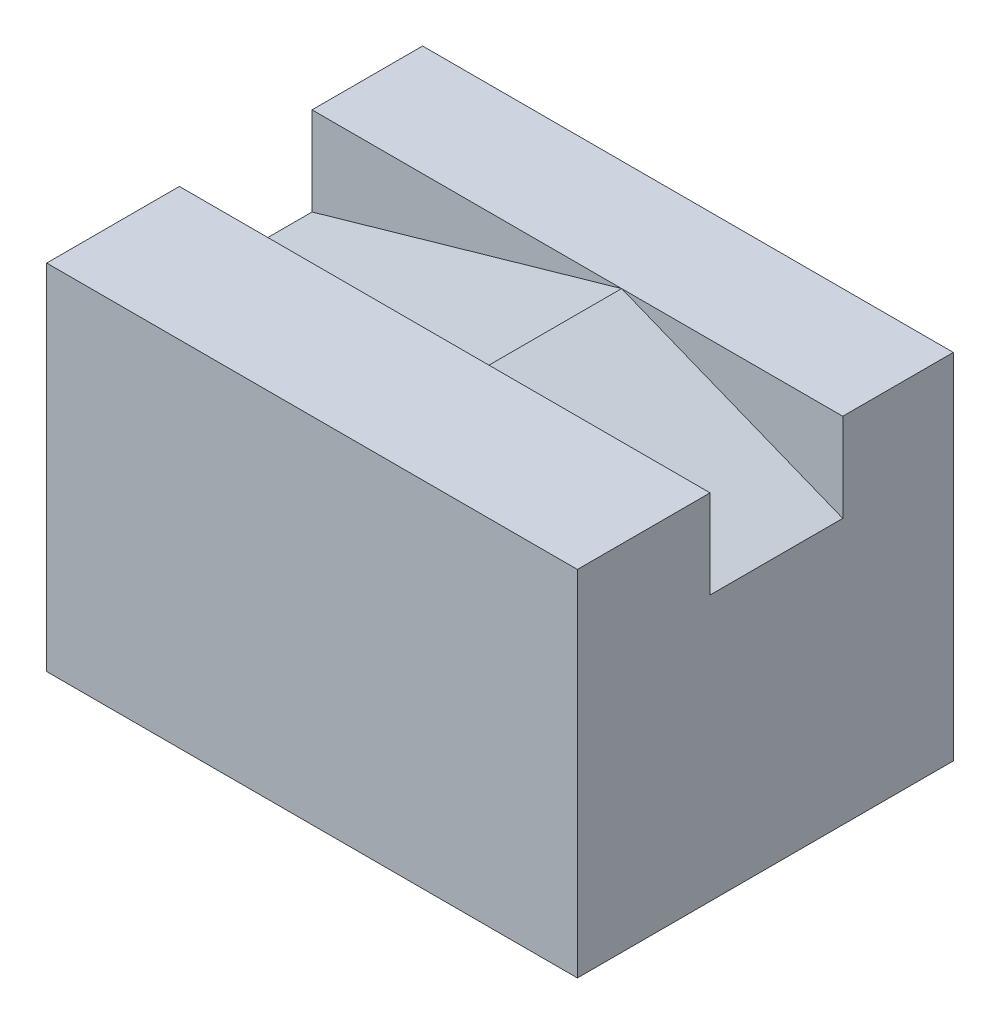
SolidWorks part; units mm, degrees
ref_plane "Front Plane" through (0, 0, 0) normal (0, 0, 1) x (1, 0, 0)
ref_plane "Top Plane" through (0, 0, 0) normal (0, 1, 0) x (1, 0, 0)
ref_plane "Right Plane" through (0, 0, 0) normal (1, 0, 0) x (0, 0, -1)
sketch "Sketch1" plane through (0, 0, 0) normal (0, 0, 1) x (1, 0, 0)
  line L0 (-3, 1) -> (0.5, 2)
  line L1 (-3, -2) -> (3, -2)
  line L2 (-3, -2) -> (-3, 2)
  line L3 (-3, 2) -> (3, 2)
  line L4 (3, -2) -> (3, 2)
  line L5 (-3, -2) -> (3, 2) construction
  line L6 (-3, 2) -> (3, -2) construction
  line L7 (0.5, 2) -> (3, 1)
  point P0 (0, 0)
  point P9 (0, 0)
  dimension "D1" = 4
  dimension "D2" = 6
  dimension "D3" = 1
  dimension "D4" = 2.5
extrude "Boss-Extrude1" add sketch "Sketch1" against normal blind 1.25 contours L3 L2 L0 | L7 L0 L2 L1 L4 | L3 L4 L1 L2 region at (-1.8333, 1.6667, 0) region at (0.0238, -0.2381, 0)
extrude "Boss-Extrude2" add sketch "Sketch1<3>" along normal blind 1.5 contours L7 L0 L2 L1 L4 region at (0.0238, -0.2381, 0)
sketch "Sketch1<3>" plane through (0, 0, 0) normal (0, 0, 1) x (1, 0, 0) same geometry as "Sketch1"
extrude "Boss-Extrude3" add sketch "Sketch1<4>" along normal blind 1.5 from surface contours L3 L2 L0 | L7 L0 L2 L1 L4 | L3 L7 L4 region at (-1.8333, 1.6667, 0) region at (0.0238, -0.2381, 0) region at (2.1667, 1.6667, 0) starting at face at (0.1, 0, 1.5)
sketch "Sketch1<4>" plane through (0, 0, 0) normal (0, 0, 1) x (1, 0, 0) same geometry as "Sketch1"
